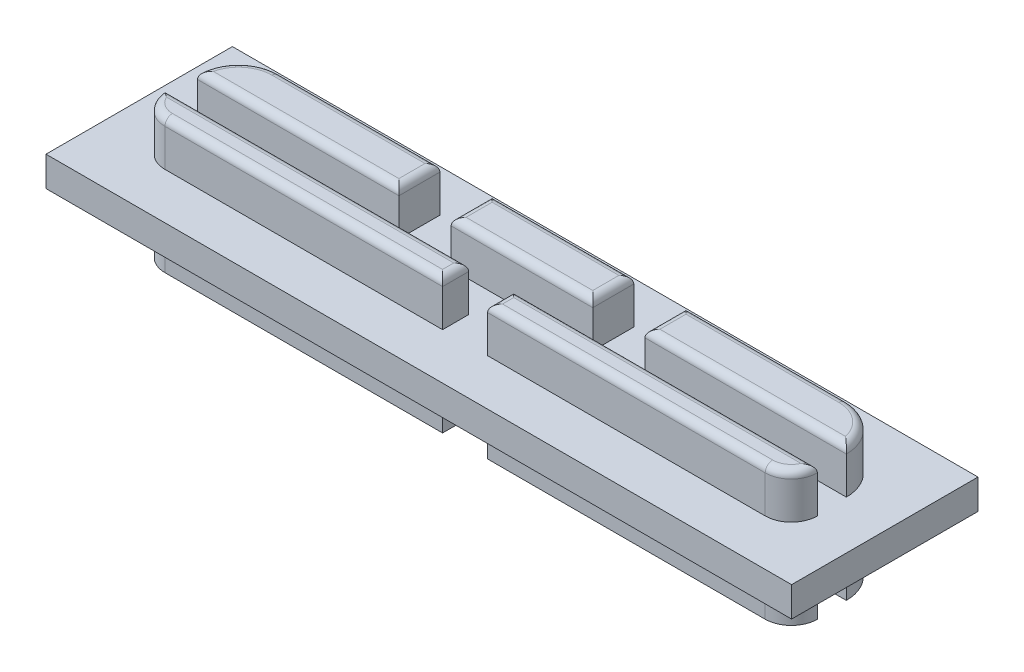
SolidWorks part; units mm, degrees
ref_plane "Front Plane" through (0, 0, 0) normal (0, 0, 1) x (1, 0, 0)
ref_plane "Top Plane" through (0, 0, 0) normal (0, 1, 0) x (1, 0, 0)
ref_plane "Right Plane" through (0, 0, 0) normal (1, 0, 0) x (0, 0, -1)
ref_plane "Plane1" through (0, 3.048, 0) normal (0, 1, 0) x (1, 0, 0)
sketch "Sketch1" plane through (0, 3.048, 0) normal (0, 1, 0) x (1, 0, 0)
  line L0 (0.0093, 27.0094) -> (0.0093, 25.6124) construction
  line L1 (-12.6907, 28.4486) -> (12.7093, 28.4486)
  line L2 (-12.6907, 28.4486) -> (-12.6907, 22.0986)
  line L3 (-12.6907, 22.0986) -> (12.7093, 22.0986)
  line L4 (12.7093, 28.4486) -> (12.7093, 22.0986)
  line L5 (-9.645, 27.0094) -> (-4.1817, 27.0094)
  line L6 (0.7761, 23.6756) -> (10.2326, 23.6756)
  line L7 (-11.042, 25.6124) -> (-4.1817, 25.6124)
  line L8 (-4.1817, 27.0094) -> (-4.1817, 25.6124)
  line L9 (-2.4037, 27.0094) -> (2.4223, 27.0094)
  line L10 (-2.4037, 27.0094) -> (-2.4037, 25.6124)
  line L11 (-2.4037, 25.6124) -> (2.4223, 25.6124)
  line L12 (2.4223, 27.0094) -> (2.4223, 25.6124)
  line L13 (4.2003, 27.0094) -> (4.2003, 25.6124)
  line L14 (11.0606, 25.6124) -> (4.2003, 25.6124)
  line L15 (9.6636, 27.0094) -> (4.2003, 27.0094)
  line L16 (0.7761, 24.5646) -> (0.7761, 23.6756)
  line L17 (-0.7575, 24.5646) -> (-11.103, 24.5646)
  line L18 (-0.7575, 24.5646) -> (-0.7575, 23.6756)
  line L19 (-0.7575, 23.6756) -> (-10.214, 23.6756)
  line L20 (0.7761, 24.5646) -> (11.1216, 24.5646)
  arc A0 (-11.042, 25.6124) -> (-9.645, 27.0094) centre (-9.645, 25.6124) cw
  arc A1 (11.0606, 25.6124) -> (9.6636, 27.0094) centre (9.6636, 25.6124) ccw
  arc A2 (-10.214, 23.6756) -> (-11.103, 24.5646) centre (-10.214, 24.5646) cw
  arc A3 (10.2326, 23.6756) -> (11.1216, 24.5646) centre (10.2326, 24.5646) ccw
  point P16 (-4.1817, 26.3109)
  point P17 (-12.6907, 25.2736)
  point P18 (0.0093, 28.4486)
  point P19 (0.0093, 27.0094)
  point P22 (4.2003, 26.3109)
  dimension "D1" = 1.397
  dimension "D2" = 0.889
  dimension "D3" = 4.826
  dimension "D4" = 1.0478
  dimension "D5" = 1.778
  dimension "D7" = 6.35
  dimension "D8" = 25.4
extrude "Boss-Extrude1" add sketch "Sketch1" along normal blind 2.032 and the other way blind 2.54 contours L8 L5 A0 L7 | L12 L9 L10 L11 | L14 A1 L15 L13 | L12 L11 L10 L9 | L19 A2 L17 L18 | L6 A3 L20 L16 region at (-7.4694, 3.048, -26.2932) region at (0.0093, 3.048, -26.3109) region at (7.488, 3.048, -26.2932)
extrude "Boss-Extrude2" add sketch "Sketch1<3>" along normal blind 0.508 and the other way blind 0.508 contours L4 L1 L2 L3 A3 L6 L16 L20 L7 A0 L5 L8 L9 L12 L11 L10 A1 L14 L13 L15 L19 A2 L17 L18 region at (0.0093, 3.048, -25.2317)
sketch "Sketch1<3>" plane through (0, 3.048, 0) normal (0, 1, 0) x (1, 0, 0) same geometry as "Sketch1"
fillet "Fillet1" radius 0.254 20 edges at (0.0093, 5.08, -25.6124) (-2.4037, 5.08, -26.3109) (0.0093, 5.08, -27.0094) (2.4223, 5.08, -26.3109) (-7.6118, 5.08, -25.6124) (-10.6328, 5.08, -26.6002) (-6.9133, 5.08, -27.0094) (-4.1817, 5.08, -26.3109) (-5.4857, 5.08, -23.6756) (-10.8426, 5.08, -23.936) (-5.9302, 5.08, -24.5646) (-0.7575, 5.08, -24.1201) (5.9488, 5.08, -24.5646) (10.8612, 5.08, -23.936) (5.5043, 5.08, -23.6756) (0.7761, 5.08, -24.1201) (4.2003, 5.08, -26.3109) (6.932, 5.08, -27.0094) (10.6514, 5.08, -26.6002) (7.6305, 5.08, -25.6124)
